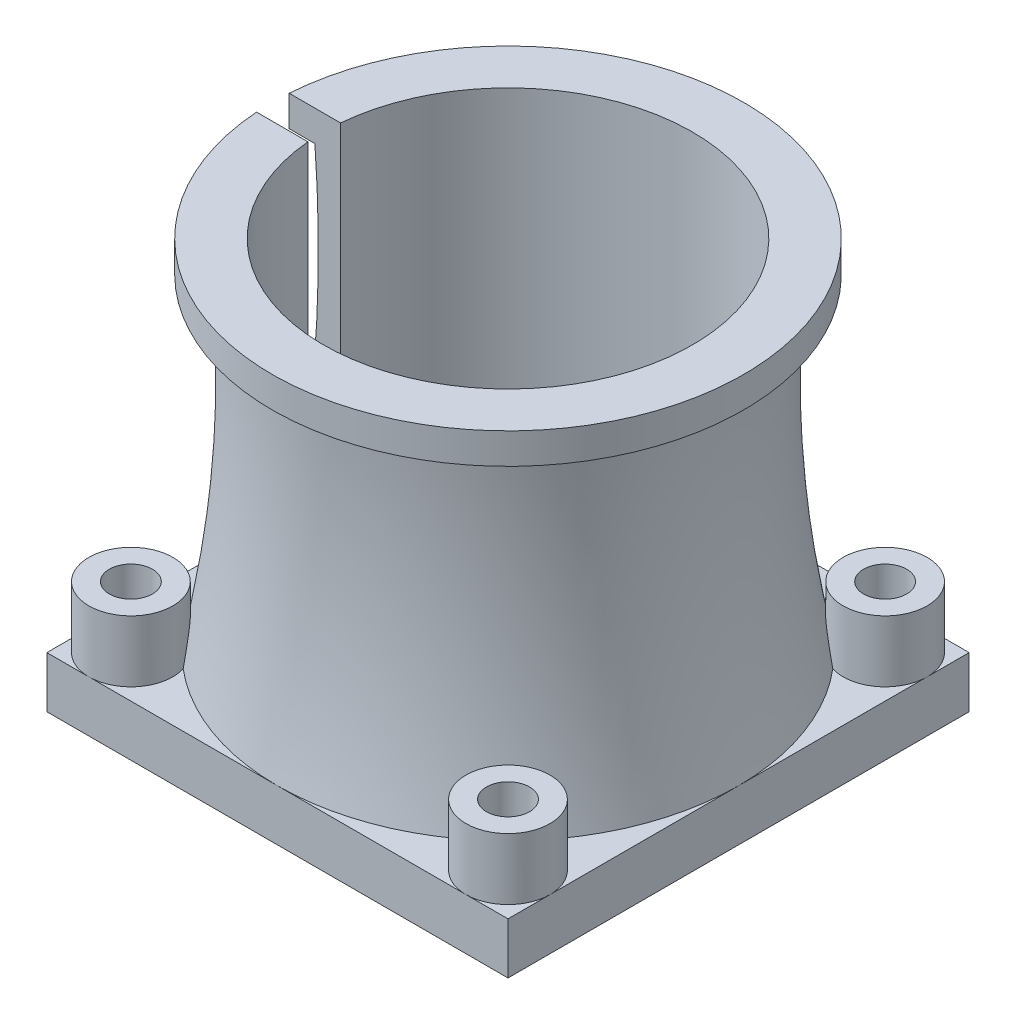
SolidWorks part; units mm, degrees
ref_plane "Front Plane" through (0, 0, 0) normal (0, 0, 1) x (1, 0, 0)
ref_plane "Top Plane" through (0, 0, 0) normal (0, 1, 0) x (1, 0, 0)
ref_plane "Right Plane" through (0, 0, 0) normal (1, 0, 0) x (0, 0, -1)
sketch "Sketch1" plane through (0, 0, 0) normal (0, 1, 0) x (1, 0, 0)
  line L1 (-22.5, 22.5) -> (22.5, 22.5)
  line L2 (-22.5, 22.5) -> (-22.5, -22.5)
  line L3 (-22.5, -22.5) -> (22.5, -22.5)
  line L4 (22.5, 22.5) -> (22.5, -22.5)
  line L5 (-22.5, 22.5) -> (22.5, -22.5) construction
  line L6 (-22.5, -22.5) -> (22.5, 22.5) construction
  circle A0 centre (0, 0) radius 17
  point P0 (0, 0)
  dimension "D3" = 34
  dimension "D1" = 45
  dimension "D2" = 45
sketch "Sketch2" plane through (0, 0, 0) normal (0, 0, 1) x (1, 0, 0)
  line L0 (-18, 40) -> (-18, 0)
  line L1 (-22.5, 0) -> (22.5, 0) construction
  line L2 (-18, 0) -> (-22.5, 0)
  line L3 (-22.5, 0) -> (22.5, 0) construction
  line L4 (-22.5, 0) -> (-22.5, 5)
  line L5 (-18, 40) -> (-23, 40)
  line L6 (-23, 40) -> (-23, 37)
  line L7 (-23, 37) -> (-20.5, 37)
  line L8 (0, 0) -> (0, 37) construction
  spline S0 degree 2 poles (-20.5, 37) (-19.2787, 20.724) (-22.5, 5) knots 0 0 0 0.828874 0.828874 0.828874
  dimension "D1" = 18
  dimension "D2" = 5
  dimension "D3" = 40
  dimension "D4" = 5
  dimension "D5" = 3
  dimension "D6" = 2.5
  dimension "D7" = 22.5
revolve "Revolve1" add sketch "Sketch2" angle 360 about L8
extrude "Boss-Extrude1" add sketch "Sketch1" along normal blind 5
sketch "Sketch3" plane through (0, 0, 0) normal (1, 0, 0) x (0, 0, -1)
  line L0 (18, 40) -> (-18, 40) construction
  line L1 (1.5928, 61.4522) -> (-1.5928, 61.4522)
  line L2 (1.5928, 61.4522) -> (1.5928, 18.5478)
  line L4 (-1.5928, 61.4522) -> (-1.5928, 18.5478)
  line L5 (1.5928, 61.4522) -> (-1.5928, 18.5478) construction
  line L6 (1.5928, 18.5478) -> (-1.5928, 61.4522) construction
  line L7 (1.5928, 18.5478) -> (0, 15.6353)
  line L8 (0, 15.6353) -> (-1.5928, 18.5478)
  point P0 (0, 40)
extrude "Cut-Extrude1" cut sketch "Sketch3" against normal through all
sketch "Sketch4" plane through (0, 0, 0) normal (0, 1, 0) x (1, 0, 0)
  line L0 (-22.5, -22.5) -> (22.5, 22.5) construction
  circle A0 centre (-18.4, -18.4) radius 2.1
  dimension "D1" = 4.2
  dimension "D2" = 18.4
extrude "Cut-Extrude3" cut sketch "Sketch4" against normal through all and the other way through all
sketch "Sketch5" plane through (0, 0, 0) normal (0, 1, 0) x (1, 0, 0)
  circle A0 centre (-18.4, -18.4) radius 4.1
  circle A1 centre (-18.4, -18.4) radius 2.1
extrude "Boss-Extrude3" add sketch "Sketch5" along normal blind 11
pattern_linear "LPattern1" count 2 spacing 36.8 along (0, 0, -1) count 2 spacing 36.8 along (1, 0, 0) of "Cut-Extrude3", "Boss-Extrude3"
fillet "Fillet3" radius 1 rebuild error yes
equation "\"D1@Sketch2\"=36/2"
equation "\"D3@LPattern1\"=18.4*2"
equation "\"D4@LPattern1\"=18.4*2"
